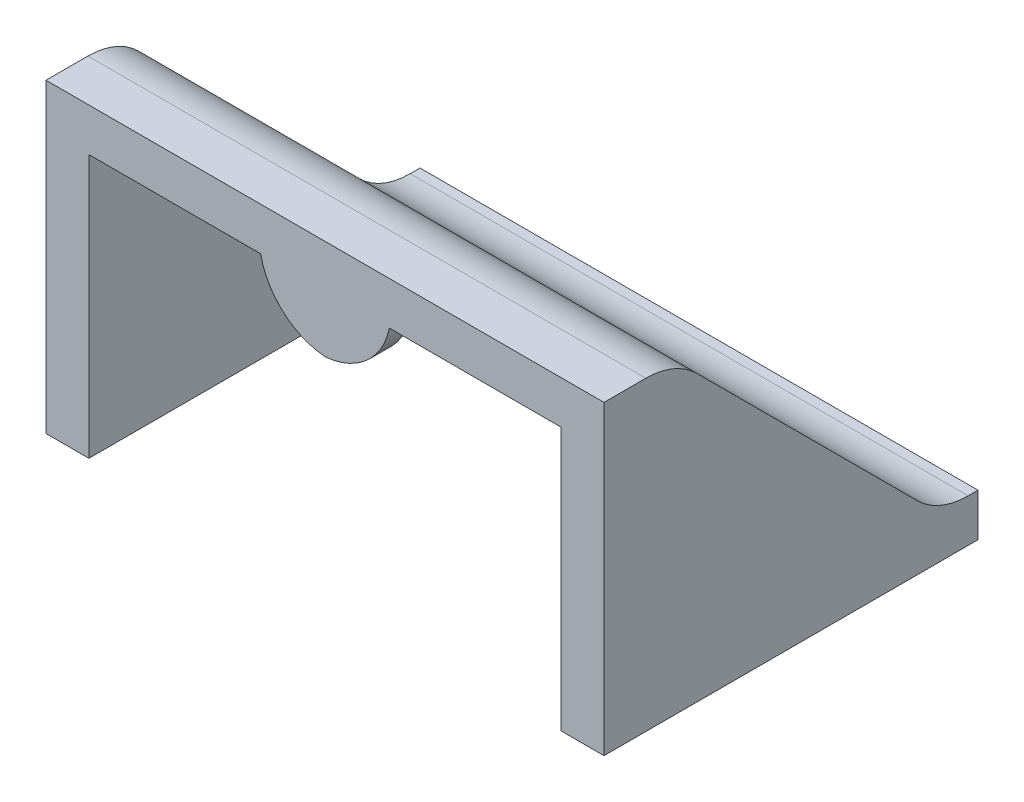
SolidWorks part; units mm, degrees
ref_plane "前视基准面" through (0, 0, 0) normal (0, 0, 1) x (1, 0, 0)
ref_plane "上视基准面" through (0, 0, 0) normal (0, 1, 0) x (1, 0, 0)
ref_plane "右视基准面" through (0, 0, 0) normal (1, 0, 0) x (0, 0, -1)
sketch "草图1" plane through (0, 0, 0) normal (0, 0, 1) x (1, 0, 0)
  line L1 (0, 0) -> (25, 0)
  line L2 (0, 0) -> (0, -10)
  line L3 (0, -10) -> (25, -10)
  line L4 (25, 0) -> (25, -10)
  dimension "301" = 25
  dimension "D2" = 10
extrude "凸台-拉伸1" add sketch "草图1" along normal blind 3
sketch "草图5" plane through (0, 0, 3) normal (0, 0, 1) x (1, 0, 0)
  line L0 (0, 0) -> (0, -10) construction
  line L1 (25, 0) -> (-2, 0)
  line L3 (27.5725, -3) -> (0, -3)
  line L6 (0, -3) -> (-8, -3)
  line L8 (-2, 0) -> (-8, 0)
  line L9 (-8, -3) -> (-8, 0)
  line L10 (27.5725, -3) -> (31, -3)
  line L12 (25, 0) -> (31, 0)
  line L13 (31, -3) -> (31, 0)
  dimension "D1" = 3
  dimension "D2" = 6
  dimension "D3" = 6
extrude "凸台-拉伸3" add sketch "草图5" along normal blind 7
sketch "草图6" plane through (31, 0, 0) normal (1, 0, 0) x (0, 0, -1)
  line L0 (-10, 0) -> (-25.3848, 15.3848)
  line L2 (-24.1421, 18.3848) -> (-5.7574, 0)
  line L3 (-10, 0) -> (-3, 0) construction
  line L4 (-5.7574, 0) -> (-10, 0)
  line L5 (-29.1421, 18.3848) -> (-29.1421, 15.3848)
  line L6 (-29.1421, 15.3848) -> (-25.3848, 15.3848)
  line L7 (-29.1421, 18.3848) -> (-24.1421, 18.3848)
  dimension "D2" = 26
  dimension "D3" = 3
  dimension "D4" = 3
  dimension "D5" = 5
extrude "凸台-拉伸4" add sketch "草图6" against normal blind 39
sketch "草图8" plane through (31, 0, 0) normal (1, 0, 0) x (0, 0, -1)
  line L0 (-29.1421, 15.3848) -> (-25.3848, 15.3848)
  line L1 (-25.3848, 15.3848) -> (-10, 0)
  line L2 (-10, 0) -> (-10, -3)
  line L3 (-10, -3) -> (-29.1421, -3)
  line L4 (-29.1421, -3) -> (-29.1421, 15.3848)
extrude "凸台-拉伸6" add sketch "草图8" against normal blind 3
sketch "草图9" plane through (-8, 0, 0) normal (-1, 0, 0) x (0, 0, 1)
  line L0 (29.1421, 15.3848) -> (25.3848, 15.3848)
  line L1 (25.3848, 15.3848) -> (10, 0)
  line L2 (10, 0) -> (10, -3)
  line L3 (10, -3) -> (29.1421, -3)
  line L4 (29.1421, -3) -> (29.1421, 15.3848)
extrude "凸台-拉伸7" add sketch "草图9" against normal blind 3
sketch "草图10" plane through (0, 0, 0) normal (0, 0, -1) x (-1, 0, 0)
  line L1 (-25, 0) -> (0, 0)
  line L2 (-25, 0) -> (-25, -10)
  line L3 (-25, -10) -> (0, -10)
  line L4 (0, 0) -> (0, -10)
extrude "切除-拉伸1" cut sketch "草图10" against normal blind 3
fillet "圆角1" radius 5 1 edges at (11.5, 18.3848, 24.1421)
fillet "圆角2" radius 5 1 edges at (11.5, 0, 5.7574)
sketch "草图12" plane through (0, 15.3848, 0) normal (0, -1, 0) x (-1, 0, 0)
  line L0 (5, -29.1421) -> (-28, -29.1421) construction
  line L1 (-7, -29.1421) -> (-16, -29.1421)
  line L2 (-7, -29.1421) -> (-7, -27.6421)
  line L3 (-7, -27.6421) -> (-16, -27.6421)
  line L4 (-16, -29.1421) -> (-16, -27.6421)
  line L5 (5, -29.1421) -> (5, -25.3848) construction
  line L6 (-28, -25.3848) -> (-28, -29.1421) construction
  dimension "D1" = 1.5
  dimension "D2" = 12
  dimension "D3" = 12
extrude "凸台-拉伸9" add sketch "草图12" along normal blind 4
fillet "圆角3" radius 5 2 edges at (16, 11.3848, 28.3921) (7, 11.3848, 28.3921)
